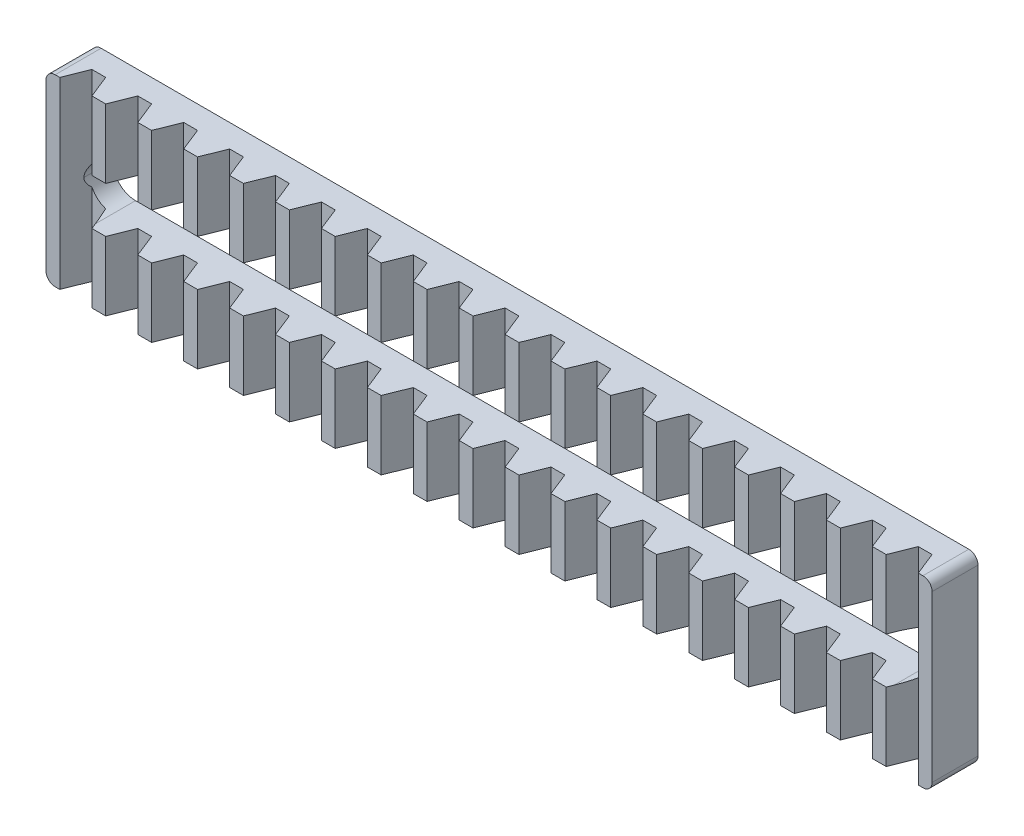
SolidWorks part; units mm, degrees
ref_plane "Front" through (0, 0, 0) normal (0, 0, 1) x (1, 0, 0)
ref_plane "Top" through (0, 0, 0) normal (0, 1, 0) x (1, 0, 0)
ref_plane "Right" through (0, 0, 0) normal (1, 0, 0) x (0, 0, -1)
sketch "Sketch1" plane through (0, 0, 0) normal (0, 1, 0) x (1, 0, 0)
  line L1 (96.5, -5) -> (-96.5, -5)
  line L2 (96.5, -5) -> (96.5, 5)
  line L3 (96.5, 5) -> (-96.5, 5)
  line L4 (-96.5, -5) -> (-96.5, 5)
  line L5 (96.5, -5) -> (-96.5, 5) construction
  line L6 (96.5, 5) -> (-96.5, -5) construction
  point P0 (0, 0)
  dimension "D1" = 10
  dimension "D2" = 193
extrude "Boss-Extrude1" add sketch "Sketch1" along normal blind 40
sketch "Sketch2" plane through (0, 0, 0) normal (0, 1, 0) x (1, 0, 0)
  line L0 (-96.5, -5) -> (-93.5, -5)
  line L1 (-96.5, -5) -> (96.5, -5) construction
  line L2 (-93.5, -5) -> (-91.5, 0)
  line L3 (-91.5, 0) -> (-88.5, 0)
  line L4 (-88.5, 0) -> (-86.5, -5)
  line L5 (-86.5, -5) -> (-83.5, -5)
  line L6 (-83.5, -5) -> (-81.5, 0)
  line L7 (-81.5, 0) -> (-78.5, 0)
  line L8 (-78.5, 0) -> (-76.5, -5)
  line L9 (-76.5, -5) -> (-73.5, -5)
  line L10 (-73.5, -5) -> (-71.5, 0)
  line L11 (-71.5, 0) -> (-68.5, 0)
  line L12 (-68.5, 0) -> (-66.5, -5)
  line L13 (-66.5, -5) -> (-63.5, -5)
  line L14 (-63.5, -5) -> (-61.5, 0)
  line L15 (-61.5, 0) -> (-58.5, 0)
  line L16 (-58.5, 0) -> (-56.5, -5)
  line L17 (-56.5, -5) -> (-53.5, -5)
  line L18 (-53.5, -5) -> (-51.5, 0)
  line L19 (-51.5, 0) -> (-48.5, 0)
  line L20 (-48.5, 0) -> (-46.5, -5)
  line L21 (-46.5, -5) -> (-43.5, -5)
  line L22 (-43.5, -5) -> (-41.5, 0)
  line L23 (-41.5, 0) -> (-38.5, 0)
  line L24 (-38.5, 0) -> (-36.5, -5)
  line L25 (-36.5, -5) -> (-33.5, -5)
  line L26 (-33.5, -5) -> (-31.5, 0)
  line L27 (-31.5, 0) -> (-28.5, 0)
  line L28 (-28.5, 0) -> (-26.5, -5)
  line L29 (-26.5, -5) -> (-23.5, -5)
  line L30 (-23.5, -5) -> (-21.5, 0)
  line L31 (-21.5, 0) -> (-18.5, 0)
  line L32 (-18.5, 0) -> (-16.5, -5)
  line L33 (-16.5, -5) -> (-13.5, -5)
  line L34 (-13.5, -5) -> (-11.5, 0)
  line L35 (-11.5, 0) -> (-8.5, 0)
  line L36 (-8.5, 0) -> (-6.5, -5)
  line L37 (-6.5, -5) -> (-3.5, -5)
  line L38 (-3.5, -5) -> (-1.5, 0)
  line L39 (-1.5, 0) -> (1.5, 0)
  line L40 (1.5, 0) -> (3.5, -5)
  line L41 (3.5, -5) -> (6.5, -5)
  line L42 (6.5, -5) -> (8.5, 0)
  line L43 (8.5, 0) -> (11.5, 0)
  line L44 (11.5, 0) -> (13.5, -5)
  line L45 (13.5, -5) -> (16.5, -5)
  line L46 (16.5, -5) -> (18.5, 0)
  line L47 (18.5, 0) -> (21.5, 0)
  line L48 (21.5, 0) -> (23.5, -5)
  line L49 (23.5, -5) -> (26.5, -5)
  line L50 (26.5, -5) -> (28.5, 0)
  line L51 (28.5, 0) -> (31.5, 0)
  line L52 (31.5, 0) -> (33.5, -5)
  line L53 (33.5, -5) -> (36.5, -5)
  line L54 (36.5, -5) -> (38.5, 0)
  line L55 (38.5, 0) -> (41.5, 0)
  line L56 (41.5, 0) -> (43.5, -5)
  line L57 (43.5, -5) -> (46.5, -5)
  line L58 (46.5, -5) -> (48.5, 0)
  line L59 (48.5, 0) -> (51.5, 0)
  line L60 (51.5, 0) -> (53.5, -5)
  line L61 (53.5, -5) -> (56.5, -5)
  line L62 (56.5, -5) -> (58.5, 0)
  line L63 (58.5, 0) -> (61.5, 0)
  line L64 (61.5, 0) -> (63.5, -5)
  line L65 (63.5, -5) -> (66.5, -5)
  line L66 (66.5, -5) -> (68.5, 0)
  line L67 (68.5, 0) -> (71.5, 0)
  line L68 (71.5, 0) -> (73.5, -5)
  line L69 (73.5, -5) -> (76.5, -5)
  line L70 (76.5, -5) -> (78.5, 0)
  line L71 (78.5, 0) -> (81.5, 0)
  line L72 (81.5, 0) -> (83.5, -5)
  line L73 (83.5, -5) -> (86.5, -5)
  line L74 (86.5, -5) -> (88.5, 0)
  line L75 (88.5, 0) -> (91.5, 0)
  line L76 (91.5, 0) -> (93.5, -5)
  line L77 (93.5, -5) -> (96.5, -5)
  line L81 (-96.5, -5) -> (-96.5, -20.768)
  line L82 (-96.5, -20.768) -> (96.5, -20.768)
  line L83 (96.5, -20.768) -> (96.5, -5)
  line L84 (101.5, 0) -> (103.5, -5) [skipped]
  line L85 (98.5, 0) -> (101.5, 0) [skipped]
  line L86 (96.5, -5) -> (98.5, 0) [skipped]
  dimension "D1" = 5
  dimension "D2" = 2
  dimension "D3" = 3
  dimension "D4" = 2
  dimension "D5" = 3
  dimension "D6" = 20
  dimension "D7" = 3
  dimension "D8" = 193
extrude "Cut-Extrude1" cut sketch "Sketch2" along normal blind 44 contours L82 L83 L77 L76 L75 L74 L73 L72 L71 L70 L69 L68 L67 L66 L65 L64 L63 L62 L61 L60 L59 L58 L57 L56 L55 L54 L53 L52 L51 L50 L49 L48 L47 L46 L45 L44 L43 L42 L41 L40 L39 L38 L37 L36 L35 L34 L33 L32 region at (0, 0, 11.5271)
sketch "Sketch3" plane through (0, 0, 0) normal (0, 0, 1) x (1, 0, 0)
  line L1 (92, 15) -> (-92, 15)
  line L2 (92, 15) -> (92, 25)
  line L3 (92, 25) -> (-92, 25)
  line L4 (-92, 15) -> (-92, 25)
  line L5 (92, 15) -> (-92, 25) construction
  line L6 (92, 25) -> (-92, 15) construction
  line L7 (91.5, 40) -> (88.5, 40) construction
  point P7 (90, 40)
  dimension "D1" = 92
  dimension "D2" = 10
  dimension "D3" = 15
  dimension "D4" = 92
  dimension "D5" = 15
extrude "Cut-Extrude2" cut sketch "Sketch3" against normal mid plane 44
fillet "Fillet1" radius 5 4 edges at (92, 15, -1.875) (92, 25, -1.875) (-92, 15, -1.875) (-92, 25, -1.875)
ref_plane "Plane1" through (0, 0, -5) normal (0, 0, 1) x (1, 0, 0)
sketch "Sketch4" plane through (0, 0, -5) normal (0, 0, 1) x (1, 0, 0)
  line L1 (-92, 30) -> (92, 30)
  line L2 (-92, 30) -> (-92, 35)
  line L3 (-92, 35) -> (92, 35)
  line L4 (92, 30) -> (92, 35)
  line L5 (-92, 30) -> (92, 35) construction
  line L6 (-92, 35) -> (92, 30) construction
  line L7 (-92, 10) -> (92, 10)
  line L8 (-92, 10) -> (-92, 5)
  line L9 (-92, 5) -> (92, 5)
  line L10 (92, 10) -> (92, 5)
  line L11 (-92, 10) -> (92, 5) construction
  line L12 (-92, 5) -> (92, 10) construction
  line L13 (-92, 28.5) -> (92, 28.5)
  line L14 (-92, 28.5) -> (-92, 36.5)
  line L15 (-92, 36.5) -> (92, 36.5)
  line L16 (92, 28.5) -> (92, 36.5)
  line L17 (-92, 28.5) -> (92, 36.5) construction
  line L18 (-92, 36.5) -> (92, 28.5) construction
  line L19 (-92, 3.5) -> (92, 3.5)
  line L20 (-92, 3.5) -> (-92, 11.5)
  line L21 (-92, 11.5) -> (92, 11.5)
  line L22 (92, 3.5) -> (92, 11.5)
  line L23 (-92, 3.5) -> (92, 11.5) construction
  line L24 (-92, 11.5) -> (92, 3.5) construction
  point P0 (0, 32.5)
  point P5 (0, 7.5)
  point P10 (0, 32.5)
  point P16 (0, 7.5)
  dimension "D1" = 184
  dimension "D2" = 184
  dimension "D3" = 5
  dimension "D4" = 5
  dimension "D5" = 7.5
  dimension "D6" = 32.5
  dimension "D7" = 8
  dimension "D8" = 4
  dimension "D9" = 8
  dimension "D10" = 4
extrude "Cut-Extrude3" cut sketch "Sketch4" along normal blind 4 contours L1 L4 L3 L2 | L10 L7 L8 L9 region at (0, 32.5, -5) region at (0, 7.5, -5)
fillet "Fillet3" radius 2 4 edges at (96.5, 0, 0) (96.5, 40, 0) (-96.5, 40, 0) (-96.5, 0, 0)
extrude "Cut-Extrude4" cut sketch "Sketch4<4>" along normal blind 2 contours L3 L16 L15 L14 | L13 L16 L1 L14 | L7 L22 L21 L20 | L19 L22 L9 L20 region at (0, 29.25, -5) region at (0, 35.75, -5) region at (0, 10.75, -5) region at (0, 4.25, -5)
sketch "Sketch4<4>" plane through (0, 0, -5) normal (0, 0, 1) x (1, 0, 0) same geometry as "Sketch4"
fillet "Fillet4" radius 2.5 8 edges at (92, 35, -2) (92, 30, -2) (-92, 35, -2) (-92, 30, -2) (-92, 10, -2) (-92, 5, -2) (92, 10, -2) (92, 5, -2)
fillet "Fillet5" radius 4 8 edges at (-92, 3.5, -4) (-92, 11.5, -4) (-92, 28.5, -4) (-92, 36.5, -4) (92, 11.5, -4) (92, 3.5, -4) (92, 28.5, -4) (92, 36.5, -4)
